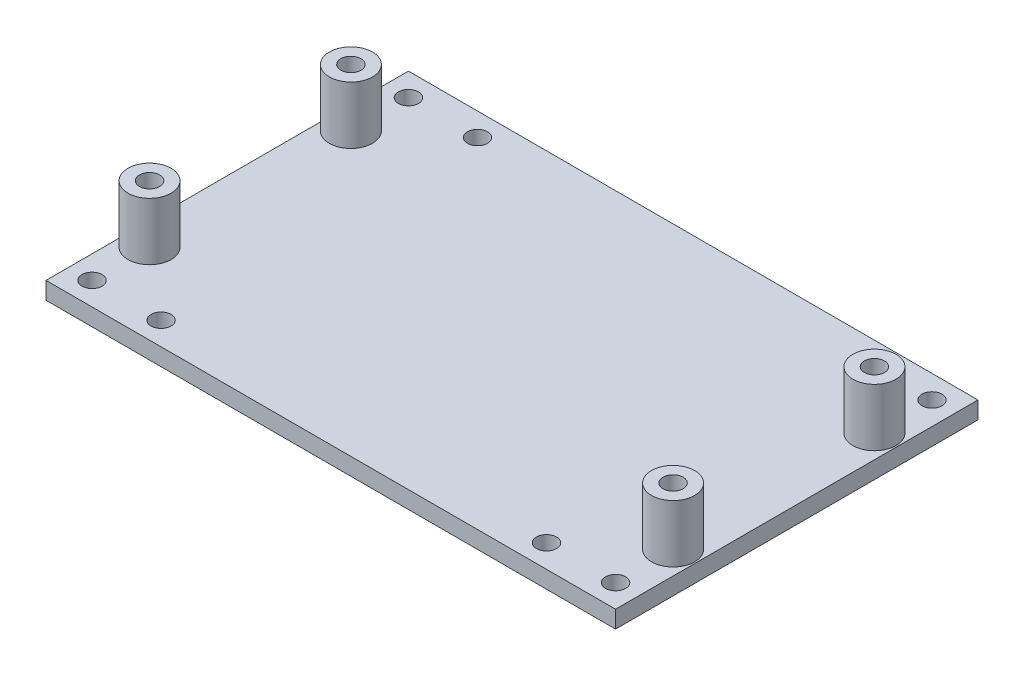
SolidWorks part; units mm, degrees
ref_plane "Płaszczyzna przednia" through (0, 0, 0) normal (0, 0, 1) x (1, 0, 0)
ref_plane "Płaszczyzna górna" through (0, 0, 0) normal (0, 1, 0) x (1, 0, 0)
ref_plane "Płaszczyzna prawa" through (0, 0, 0) normal (1, 0, 0) x (0, 0, -1)
sketch "Sketch1" plane through (0, 0, 0) normal (0, 1, 0) x (1, 0, 0)
  line L0 (-67.5377, 0) -> (67.5377, 0) construction
  line L1 (-45.5, 17.5) -> (45.5, 17.5) construction
  line L2 (-45.5, 17.5) -> (-45.5, -17.5) construction
  line L3 (-45.5, -17.5) -> (45.5, -17.5) construction
  line L4 (45.5, 17.5) -> (45.5, -17.5) construction
  line L5 (-45.5, 17.5) -> (45.5, -17.5) construction
  line L6 (-45.5, -17.5) -> (45.5, 17.5) construction
  line L7 (0, 37.1304) -> (0, -37.1304) construction
  line L8 (-49.5, 21.5) -> (-49.5, -21.5)
  line L9 (-49.5, -21.5) -> (49.5, -21.5)
  line L10 (49.5, 21.5) -> (49.5, -21.5)
  line L11 (-49.5, 21.5) -> (49.5, 21.5)
  line L12 (-49.5, 31.5) -> (49.5, 31.5)
  line L13 (-49.5, -31.5) -> (49.5, -31.5)
  line L14 (-49.5, 31.5) -> (-49.5, 21.5)
  line L15 (-49.5, -21.5) -> (-49.5, -31.5)
  line L16 (49.5, 31.5) -> (49.5, 21.5)
  line L17 (49.5, -21.5) -> (49.5, -31.5)
  circle A0 centre (-45.5, 17.5) radius 1.75
  circle A1 centre (-45.5, -17.5) radius 1.75
  circle A2 centre (45.5, -17.5) radius 1.75
  circle A3 centre (45.5, 17.5) radius 1.75
  circle A4 centre (-45.5, 17.5) radius 3.75
  circle A5 centre (-45.5, -17.5) radius 3.75
  circle A6 centre (45.5, -17.5) radius 3.75
  circle A7 centre (45.5, 17.5) radius 3.75
  circle A8 centre (-45.5, 27.5) radius 1.75
  circle A9 centre (45.5, 27.5) radius 1.75
  circle A10 centre (45.5, -27.5) radius 1.75
  circle A11 centre (-45.5, -27.5) radius 1.75
  circle A12 centre (-33.5, 27.5) radius 1.75
  circle A13 centre (33.5, 27.5) radius 1.75
  circle A14 centre (33.5, -27.5) radius 1.75
  circle A15 centre (-33.5, -27.5) radius 1.75
  point P0 (0, 0)
  point P43 (0, 0)
  dimension "D1" = 3.5
  dimension "D8" = 3.5
  dimension "D11" = 3.5
  dimension "D2" = 91
  dimension "D3" = 35
  dimension "D7" = 2
  dimension "D9" = 4
  dimension "D10" = 4
  dimension "D12" = 4
  dimension "D13" = 16
  dimension "D4" = 4
  dimension "D5" = 10
  dimension "D6" = 10
extrude "Boss-Extrude1" add sketch "Sketch1" along normal blind 3 contours L16 L12 L14 L11 | L11 L8 L9 L10 A5 A4 A6 A7 | L17 L9 L15 L13 region at (0, 0, 0) region at (0, 0, -26.4596) region at (0, 0, 26.4596)
extrude "Boss-Extrude2" add sketch "Sketch1<3>" along normal blind 13 contours A5 A1 | A4 A0 | A7 | A6 | A2 | A3 region at (-49.1439, 0, -17.5) region at (-49.1439, 0, 17.5)
sketch "Sketch1<3>" plane through (0, 0, 0) normal (0, 1, 0) x (1, 0, 0) same geometry as "Sketch1"
